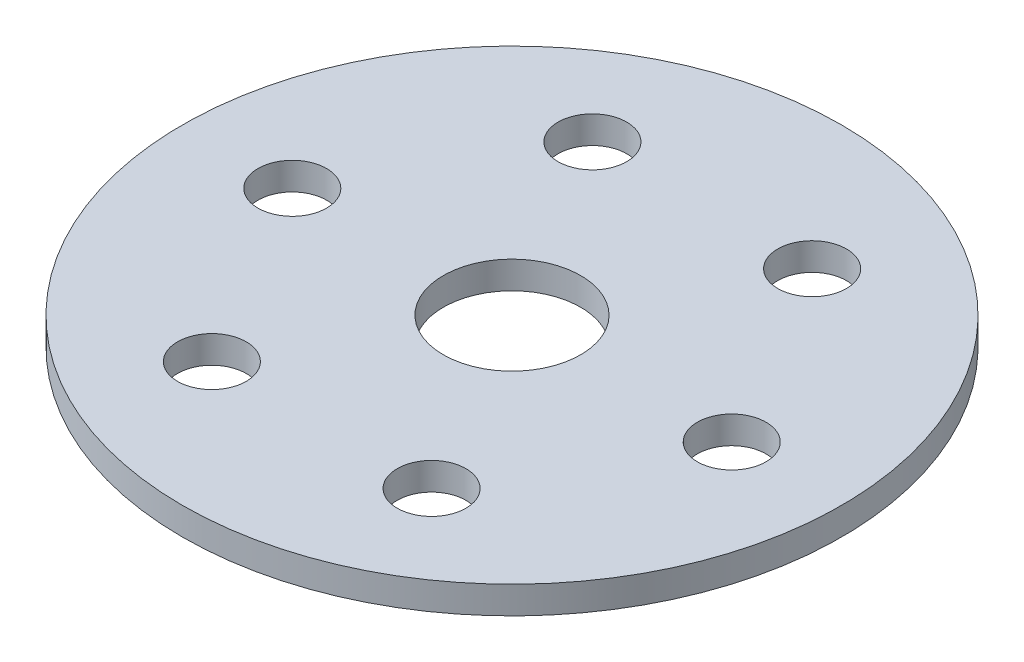
SolidWorks part; units mm, degrees
ref_plane "Front Plane" through (0, 0, 0) normal (0, 0, 1) x (1, 0, 0)
ref_plane "Top Plane" through (0, 0, 0) normal (0, 1, 0) x (1, 0, 0)
ref_plane "Right Plane" through (0, 0, 0) normal (1, 0, 0) x (0, 0, -1)
sketch "Sketch1" plane through (0, 0, 0) normal (0, 1, 0) x (1, 0, 0)
  circle A0 centre (0, 0) radius 76.2
  circle A1 centre (0, 0) radius 15.875
  dimension "D1" = 152.4
  dimension "D2" = 31.75
extrude "Plate extrude" add sketch "Sketch1" along normal blind 6.35
hole_wizard "5/8 (0.625) Diameter Hole1" positions "Sketch2" profile "Sketch3" hole size "5/8" standard "ANSI Inch" end condition through all
sketch "Sketch2" plane through (0, 6.35, 0) normal (0, 1, 0) x (1, 0, 0)
  line L0 (-3.4925, 0) -> (3.4925, 0) construction
  circle A2 centre (0, 0) radius 76.2 construction
  point P0 (-50.8, 0)
  point P3 (0, 0)
  point P5 (0, 0)
  point P10 (0, 0)
  point P11 (0, 0)
  point P14 (0, 0)
  dimension "D1" = 50.8
sketch "Sketch3" plane through (-50.8, 6.35, 0) normal (1, 0, 0) x (0, 0, 1)
  line L0 (0, 0) -> (0, 6.35)
  line L1 (0, 6.35) -> (7.9375, 6.35)
  line L2 (7.9375, 6.35) -> (7.9375, 0)
  line L5 (7.9375, 0) -> (0, 0)
  line L11 (0, -6.35) -> (0, 107.95) construction
  dimension "Thru Hole Dia." = 15.875
  dimension "Thru Hole Depth" = 6.35
pattern_circular "CirPattern1" count 6 over 360 about axis through (0, 6.35, 0) along (0, -1, 0) of "5/8 (0.625) Diameter Hole1" reverse direction yes
